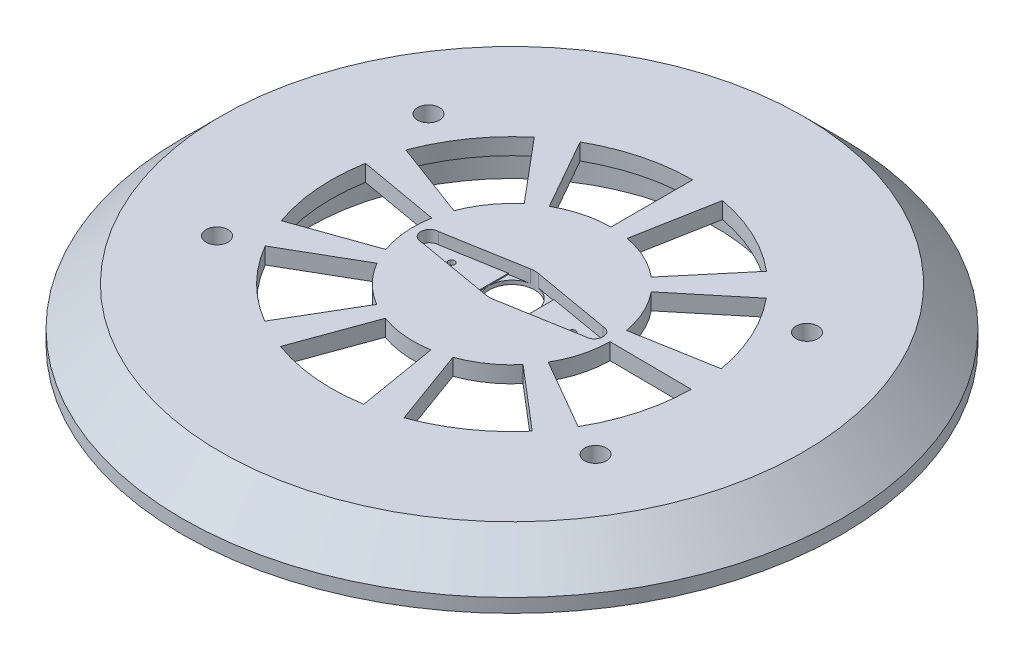
SolidWorks part; units mm, degrees
ref_plane "Front Plane" through (0, 0, 0) normal (0, 0, 1) x (1, 0, 0)
ref_plane "Top Plane" through (0, 0, 0) normal (0, 1, 0) x (1, 0, 0)
ref_plane "Right Plane" through (0, 0, 0) normal (1, 0, 0) x (0, 0, -1)
sketch "Sketch1" plane through (0, 0, 0) normal (0, 1, 0) x (1, 0, 0)
  line L4 (-11.5702, 13.7888) -> (-21.1431, 25.1974)
  line L21 (-8.8729, 15.6611) -> (-16.2142, 28.6188)
  line L22 (0, 18) -> (0, 32.8928)
  line L23 (3.2697, 17.7005) -> (5.975, 32.3456)
  line L24 (11.5702, 13.7888) -> (21.1431, 25.1974)
  line L25 (13.8824, 11.4577) -> (25.3685, 20.9375)
  line L26 (17.7265, 3.1257) -> (32.3931, 5.7118)
  line L28 (15.5885, -9) -> (28.486, -16.4464)
  line L29 (13.6943, -11.6819) -> (25.0246, -21.3473)
  line L30 (6.1564, -16.9145) -> (11.25, -30.9092)
  line L31 (2.9814, -17.7514) -> (5.4482, -32.4385)
  line L32 (-6.1564, -16.9145) -> (-11.25, -30.9092)
  line L33 (-9.1265, -15.5148) -> (-16.6775, -28.3514)
  line L34 (-15.5885, -9) -> (-28.486, -16.4464)
  line L35 (-16.964, -6.0186) -> (-30.9996, -10.9983)
  line L37 (-17.7265, 3.1257) -> (-32.3931, 5.7118)
  line L38 (-16.8638, 6.2937) -> (-30.8167, 11.501)
  line L39 (17.9994, -0.1464) -> (32.8918, -0.2675)
  circle A0 centre (0, 0) radius 60
  circle A1 centre (0, 0) radius 56.4
  circle A2 centre (0, 0) radius 40.6
  circle A4 centre (0, 0) radius 4.15
  circle A5 centre (-11, 0) radius 0.6
  circle A6 centre (11, 0) radius 0.6
  arc A8 (0, 32.8928) -> (-16.2142, 28.6188) centre (0, 0) ccw
  arc A10 (-21.1431, 25.1974) -> (-30.8167, 11.501) centre (0, 0) ccw
  arc A12 (21.1431, 25.1974) -> (5.975, 32.3456) centre (0, 0) ccw
  arc A14 (32.3931, 5.7118) -> (25.3685, 20.9375) centre (0, 0) ccw
  arc A16 (28.486, -16.4464) -> (32.8918, -0.2675) centre (0, 0) ccw
  arc A17 (11.25, -30.9092) -> (25.0246, -21.3473) centre (0, 0) ccw
  arc A20 (-11.25, -30.9092) -> (5.4482, -32.4385) centre (0, 0) ccw
  arc A22 (-28.486, -16.4464) -> (-16.6775, -28.3514) centre (0, 0) ccw
  arc A24 (-32.3931, 5.7118) -> (-30.9996, -10.9983) centre (0, 0) ccw
  circle A25 centre (0, 0) radius 37
  arc A26 (0, 18) -> (-8.8729, 15.6611) centre (0, 0) ccw
  arc A27 (11.5702, 13.7888) -> (3.2697, 17.7005) centre (0, 0) ccw
  arc A28 (17.7265, 3.1257) -> (13.8824, 11.4577) centre (0, 0) ccw
  arc A29 (15.5885, -9) -> (17.9994, -0.1464) centre (0, 0) ccw
  arc A30 (6.1564, -16.9145) -> (13.6943, -11.6819) centre (0, 0) ccw
  arc A31 (-6.1564, -16.9145) -> (2.9814, -17.7514) centre (0, 0) ccw
  arc A32 (-15.5885, -9) -> (-9.1265, -15.5148) centre (0, 0) ccw
  arc A33 (-17.7265, 3.1257) -> (-16.964, -6.0186) centre (0, 0) ccw
  arc A34 (-11.5702, 13.7888) -> (-16.8638, 6.2937) centre (0, 0) ccw
  point P36 (0, 0)
  dimension "D1" = 120
  dimension "D2" = 112.8
  dimension "D3" = 81.2
  dimension "D4" = 74
extrude "Boss-Extrude1" add sketch "Sketch1" along normal blind 3 contours A4 A5 A6 | A2 | A1 A2 | A0 A1 region at (-58.3029, 0, 0) region at (-54.8048, 0, 0) region at (-39.4517, 0, 0) region at (-35.9535, 0, 0)
extrude "Boss-Extrude2" add sketch "Sketch1<5>" against normal blind 6.5 contours A0 A1 | A2 region at (-58.3029, 0, 0) region at (-39.4517, 0, 0)
sketch "Sketch1<5>" plane through (0, 0, 0) normal (0, 1, 0) x (1, 0, 0) same geometry as "Sketch1"
fillet "Fillet1" radius 8 2 edges at (0, 0, 56.4) (0, 0, 40.6)
chamfer "Chamfer1" distance 7 angle 45 1 edges at (0, 3, 60)
sketch "Sketch2" plane through (0, 3, 0) normal (0, 1, 0) x (1, 0, 0)
  line L1 (0.7121, -4.0885) -> (15, -1.6)
  line L2 (0.7121, 4.0885) -> (15, 1.6)
  line L3 (0, -4.15) -> (0, -12.3871) construction
  line L4 (-0.7121, 4.0885) -> (-15, 1.6)
  line L5 (-0.7121, -4.0885) -> (-15, -1.6)
  arc A0 (-0.7121, -4.0885) -> (0.7121, -4.0885) centre (0, 0) ccw
  arc A1 (15, -1.6) -> (15, 1.6) centre (15, 0) ccw
  arc A2 (-15, -1.6) -> (-15, 1.6) centre (-15, 0) cw
  arc A3 (0.7121, 4.0885) -> (-0.7121, 4.0885) centre (0, 0) ccw
  dimension "D1" = 3.2
extrude "Cut-Extrude1" cut sketch "Sketch2" against normal blind 2.1
sketch "Sketch3" plane through (0, 3, 0) normal (0, 1, 0) x (1, 0, 0)
  line L0 (-34.4583, 0) -> (34.4583, 0) construction
  line L1 (34.4583, -19.25) -> (-34.4583, -19.25) construction
  line L2 (34.4583, -19.25) -> (34.4583, 19.25) construction
  line L3 (34.4583, 19.25) -> (-34.4583, 19.25) construction
  line L4 (-34.4583, -19.25) -> (-34.4583, 19.25) construction
  circle A0 centre (0, 0) radius 39.4707 construction
  circle A1 centre (-34.4583, -19.25) radius 2
  circle A2 centre (-34.4583, 19.25) radius 2
  circle A3 centre (34.4583, 19.25) radius 2
  circle A4 centre (34.4583, -19.25) radius 2
  circle A5 centre (34.4583, -19.25) radius 3.85 construction
  circle A6 centre (34.4583, 19.25) radius 3.85 construction
  circle A7 centre (-34.4583, 19.25) radius 3.85 construction
  circle A8 centre (-34.4583, -19.25) radius 3.85 construction
  point P17 (0, 0)
  dimension "D1" = 38.5
  dimension "D2" = 68.9166
extrude "Cut-Extrude2" cut sketch "Sketch3" against normal blind 5
fillet "Fillet2" radius 5 2 edges at (0, -6.5, 56.4) (0, -6.5, 40.6)
sketch "Sketch4" plane through (0, 0.9, 0) normal (0, 1, 0) x (1, 0, 0)
  line L0 (-0.7121, 4.0885) -> (-15, 1.6) construction
  line L1 (-15, -1.6) -> (-0.7121, -4.0885) construction
  line L2 (0.7121, -4.0885) -> (15, -1.6) construction
  line L3 (15, 1.6) -> (0.7121, 4.0885) construction
  line L4 (-0.7121, 4.0885) -> (-15, 1.6)
  line L5 (-15, -1.6) -> (-0.7121, -4.0885)
  line L6 (0.7121, -4.0885) -> (15, -1.6)
  line L7 (15, 1.6) -> (0.7121, 4.0885)
  line L8 (-4.15, 3.4897) -> (-4.15, -3.4897)
  line L9 (4.15, 3.4897) -> (4.15, -3.4897)
  arc A0 (-15, 1.6) -> (-15, -1.6) centre (-15, 0) ccw construction
  arc A1 (-0.7121, 4.0885) -> (-0.7121, -4.0885) centre (0, 0) ccw construction
  arc A2 (15, -1.6) -> (15, 1.6) centre (15, 0) ccw construction
  arc A3 (0.7121, -4.0885) -> (0.7121, 4.0885) centre (0, 0) ccw construction
  arc A4 (-15, 1.6) -> (-15, -1.6) centre (-15, 0) ccw
  arc A5 (-0.7121, 4.0885) -> (-0.7121, -4.0885) centre (0, 0) ccw
  arc A6 (15, -1.6) -> (15, 1.6) centre (15, 0) ccw
  arc A7 (0.7121, -4.0885) -> (0.7121, 4.0885) centre (0, 0) ccw
  line M11 (-0.7121, 4.0885) -> (-15, 1.6)
  arc M14 (-0.7121, -4.0885) -> (-0.7121, 4.0885) centre (0, 0) cw
extrude "Cut-Extrude4" cut sketch "Sketch4" against normal blind 0.2 contours L8 M11 M14 | L8 L5 M14 | A7 L9 L7 | A7 L6 L9 region at (-3.4001, 0.9, -2.8591) region at (-3.4001, 0.9, 2.8591) region at (3.4001, 0.9, 2.8591) region at (3.4001, 0.9, -2.8591)
